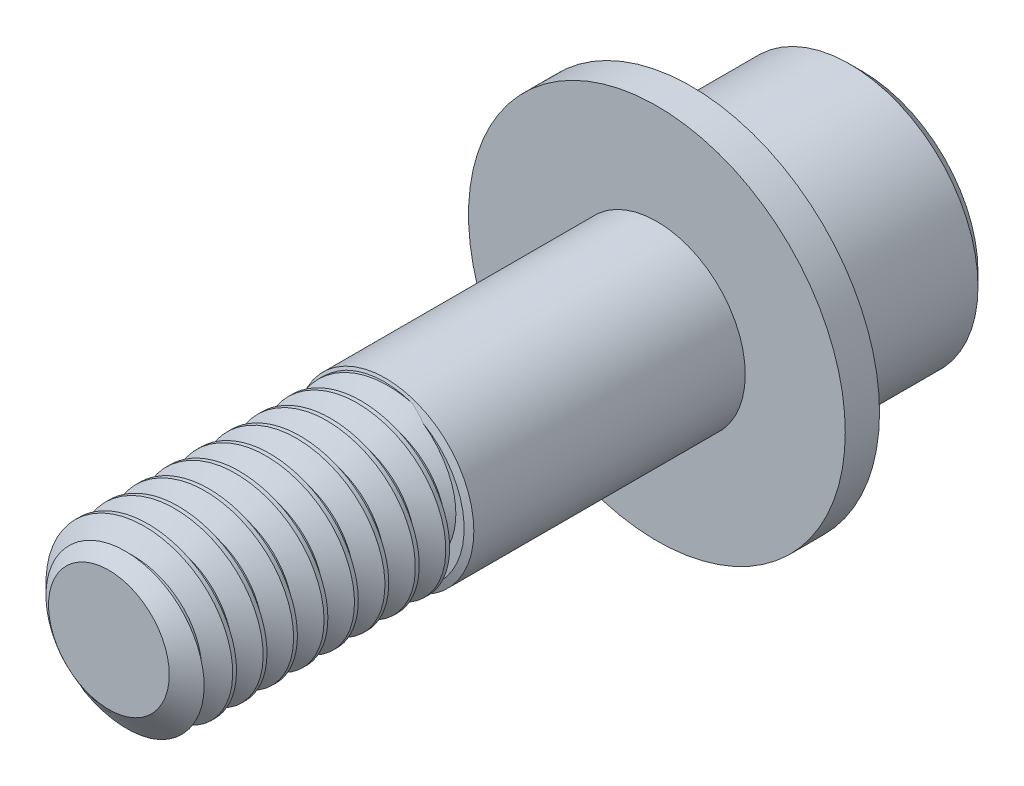
SolidWorks part; units mm, degrees
ref_plane "Front Plane" through (0, 0, 0) normal (0, 0, 1) x (1, 0, 0)
ref_plane "Top Plane" through (0, 0, 0) normal (0, 1, 0) x (1, 0, 0)
ref_plane "Right Plane" through (0, 0, 0) normal (1, 0, 0) x (0, 0, -1)
sketch "Sketch1" plane through (0, 0, 0) normal (0, 0, 1) x (1, 0, 0)
  circle A0 centre (0, 0) radius 3.9688
  dimension "OD" = 7.9375
extrude "Extrude1" add sketch "Sketch1" against normal blind 25.4
sketch "Sketch2" plane through (0, 0, 0) normal (0, 0, 1) x (1, 0, 0)
  circle A0 centre (0, 0) radius 3.9688 construction
  circle A1 centre (0, 0) radius 3.9688
curve "Helix/Spiral1" pitch 1.4111 height 26.8111 turns 19 parameters "pitch"=1.4111
sketch "Sketch3" plane through (0, 0, 0) normal (1, 0, 0) x (0, 0, -1)
  line L0 (-1.2347, 3.9688) -> (-0.7056, 3.0522)
  line L1 (-0.7056, 3.0522) -> (-0.5292, 3.0522)
  line L2 (-0.5292, 3.0522) -> (0, 3.9688)
  line L3 (-1.2347, 3.9688) -> (0, 3.9688)
  line L4 (-0.6174, 3.9688) -> (-0.6174, 3.0522) construction
  line L5 (-0.9701, 3.5105) -> (-0.2646, 3.5105) construction
  line L6 (0, 3.9688) -> (0, -3.9688) construction
  dimension "D1" = 0.1764
  dimension "D2" = 0.7056
  dimension "D3" = 60
sweep "Cut-Sweep1" cut profiles "Sketch3" path "Helix/Spiral1"
sketch "Sketch4" plane through (0, 0, 0) normal (1, 0, 0) x (0, 0, -1)
  line L0 (0.8196, 3.9688) -> (0, 2.7982)
  line L1 (0, 2.7982) -> (0, 3.9688)
  line L2 (0.8196, 3.9688) -> (0, 3.9688)
  line L3 (-1.2347, 3.9688) -> (0, 3.9688) construction
  line L4 (0, 0) -> (7.0209, 0) construction
  dimension "D1" = 55
  dimension "D2" = 0.254
revolve "Cut-Revolve1" cut sketch "Sketch4" angle 360 about L4
sketch "Sketch5" plane through (0, 0, 0) normal (1, 0, 0) x (0, 0, -1)
  line L0 (25.4, -3.0736) -> (25.4, 2.8318) construction
  line L1 (25.4, 4.0958) -> (12.8202, 4.0958)
  line L2 (25.4, 4.0958) -> (25.4, 0)
  line L3 (25.4, 0) -> (12.7, 0)
  line L4 (12.7, 3.7656) -> (12.7, 0)
  line L5 (12.8202, 4.0958) -> (12.7, 3.7656)
  line L6 (0, 0) -> (9.9695, 0) construction
  point P3 (12.7, 4.0958)
  point P10 (12.7, 4.0958)
  dimension "D1" = 0.3302
  dimension "Thread min" = 12.7
  dimension "D2" = 0.127
  dimension "D3" = 20
revolve "partially thread" add sketch "Sketch5" angle 360 about L6
sketch "Sketch6" plane through (0, 0, -25.4) normal (0, 0, -1) x (-1, 0, 0)
  circle A0 centre (0, 0) radius 5.9531
  dimension "head dia" = 11.9062
extrude "Extrude2" add sketch "Sketch6" along normal blind 9.525
sketch "Sketch10" plane through (0, 0, -25.4) normal (0, 0, 1) x (1, 0, 0)
  circle A0 centre (0, 0) radius 8.7312
  dimension "Flange Diameter" = 17.4625
extrude "Boss-Extrude1" add sketch "Sketch10" against normal blind 1.5875
sketch "Sketch7" plane through (0, 0, -34.925) normal (0, 0, -1) x (-1, 0, 0)
  line L1 (0, 3.6662) -> (-3.175, 1.8331)
  line L2 (-3.175, 1.8331) -> (-3.175, -1.8331)
  line L3 (-3.175, -1.8331) -> (0, -3.6662)
  line L4 (0, -3.6662) -> (3.175, -1.8331)
  line L5 (3.175, -1.8331) -> (3.175, 1.8331)
  line L6 (3.175, 1.8331) -> (0, 3.6662)
  circle A0 centre (0, 0) radius 3.175 construction
  dimension "hex dia" = 6.35
extrude "Cut-Extrude1" cut sketch "Sketch7" against normal blind 4.7625
sketch "Sketch8" plane through (0, 0, -34.925) normal (0, 0, -1) x (-1, 0, 0)
  circle A0 centre (0, 0) radius 3.6662
extrude "Cut-Extrude2" cut sketch "Sketch8" against normal through all draft 45
chamfer "Chamfer1" distance 0.5953 angle 45 1 edges at (-5.9531, 0, -34.925)
sketch "Sketch9" plane through (0, 0, 0) normal (1, 0, 0) x (0, 0, -1)
  line L0 (0, 3.9688) -> (0, -3.9688) construction
  line L1 (7.7611, 3.9688) -> (7.7611, -3.9688) construction
  line L2 (0, -3.9688) -> (7.7611, -3.9688) construction
  line L3 (0, 3.9688) -> (7.7611, 3.9688) construction
  dimension "D1" = 7.7611
fillet "Fillet1" radius 0.3969 1 edges at (5.9531, 0, -26.9875)
equation "\"D3@Helix/Spiral1\" = \"screw length@Extrude1\"+\"pitch@Helix/Spiral1\""
equation "\"D1@Sketch3\" = \"pitch@Helix/Spiral1\"*.125"
equation "\"D2@Sketch3\" = \"pitch@Helix/Spiral1\"*.5"
equation "\"D1@Cut-Extrude1\" = \"hex dia@Sketch7\"*.75"
equation "\"D1@Chamfer1\" = \"head dia@Sketch6\"*.05"
equation "\"D1@Sketch9\" = \"pitch@Helix/Spiral1\"*5.5"
